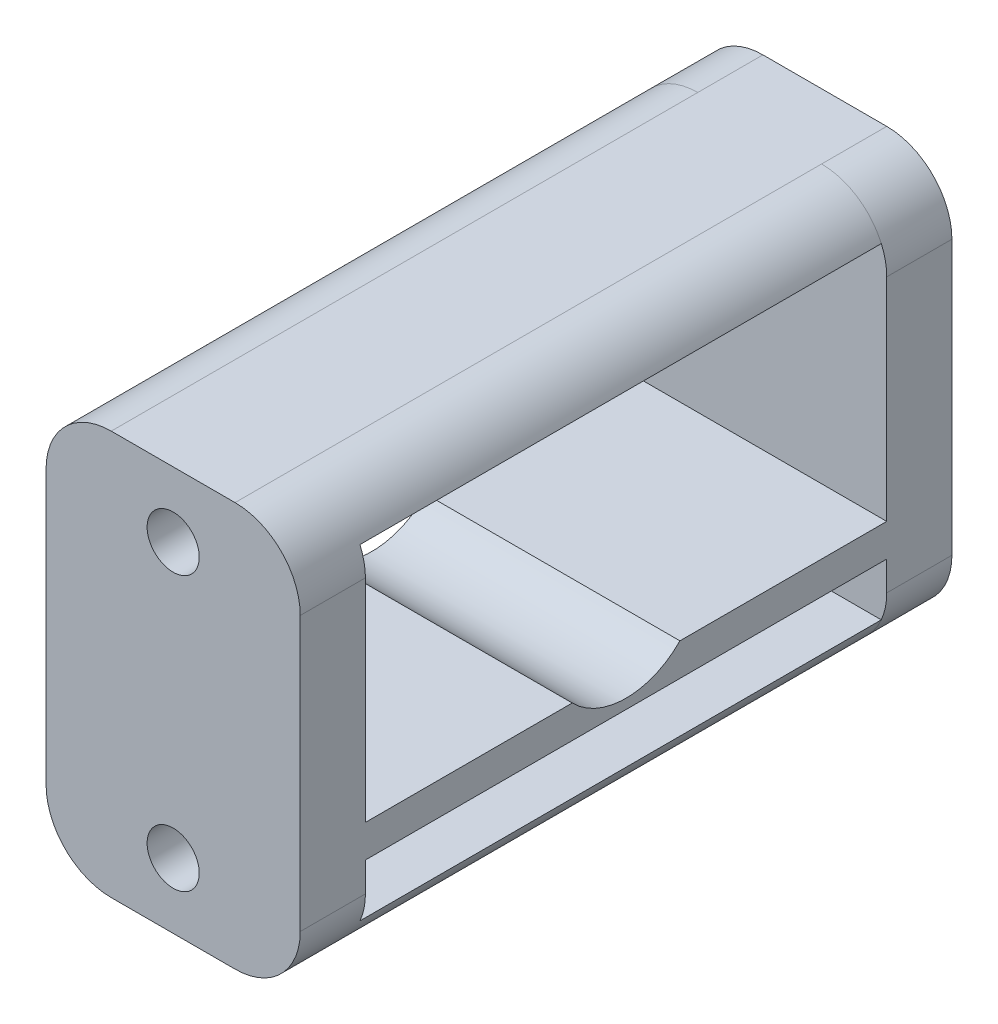
SolidWorks part; units mm, degrees
ref_plane "Plan de face" through (0, 0, 0) normal (0, 0, 1) x (1, 0, 0)
ref_plane "Plan de dessus" through (0, 0, 0) normal (0, 1, 0) x (1, 0, 0)
ref_plane "Plan de droite" through (0, 0, 0) normal (1, 0, 0) x (0, 0, -1)
sketch "Esquisse1" plane through (0, 0, 0) normal (0, 0, 1) x (1, 0, 0)
  line L1 (-19.5, -31) -> (19.5, -31)
  line L2 (-19.5, -31) -> (-19.5, 31)
  line L3 (-19.5, 31) -> (19.5, 31)
  line L4 (19.5, -31) -> (19.5, 31)
  line L5 (-19.5, -31) -> (19.5, 31) construction
  line L6 (-19.5, 31) -> (19.5, -31) construction
  point P0 (0, 0)
  dimension "D1" = 62
  dimension "D2" = 39
extrude "Boss.-Extru.1" add sketch "Esquisse1" along normal blind 10 contours L2 L1 L4 L3
sketch "Esquisse2" plane through (0, 0, 10) normal (0, 0, 1) x (1, 0, 0)
  line L0 (0, 31) -> (0, 21) construction
  line L1 (-19.5, 31) -> (19.5, 31) construction
  line L2 (0, -31) -> (0, -21) construction
  line L3 (-19.5, -31) -> (19.5, -31) construction
  circle A0 centre (0, 21) radius 4
  circle A1 centre (0, -21) radius 4
  dimension "D3" = 8
  dimension "D4" = 8
  dimension "D1" = 10
  dimension "D2" = 10
extrude "Enlèv. mat.-Extru.1" cut sketch "Esquisse2" against normal blind 10
fillet "Congé1" radius 10 4 edges at (-19.5, -31, 5) (19.5, -31, 5) (19.5, 31, 5) (-19.5, 31, 5)
sketch "Esquisse3" plane through (0, 0, 10) normal (0, 0, 1) x (1, 0, 0)
  line L0 (0, 25) -> (19.5, 25)
  line L1 (19.5, 25) -> (19.5, 31)
  line L2 (19.5, 31) -> (-19.5, 31)
  line L3 (-19.5, 31) -> (-19.5, 25)
  line L4 (-19.5, 25) -> (0, 25)
  line L5 (19.5, -21) -> (19.5, 21) construction
  line L6 (0, -25) -> (19.5, -25)
  line L7 (19.5, -25) -> (19.5, -31)
  line L8 (19.5, -31) -> (-19.5, -31)
  line L9 (-19.5, -31) -> (-19.5, -25)
  line L10 (-19.5, -25) -> (0, -25)
  line L11 (-9.5, -31) -> (9.5, -31) construction
  circle A0 centre (0, 21) radius 4 construction
  circle A1 centre (0, -21) radius 4 construction
  dimension "D1" = 39
  dimension "D2" = 0
  dimension "D3" = 0
extrude "Boss.-Extru.2" add sketch "Esquisse3" along normal blind 80
fillet "Congé2" radius 10 4 edges at (-19.5, 31, 50) (19.5, 31, 50) (-19.5, -31, 50) (19.5, -31, 50)
sketch "Esquisse4" plane through (0, 0, 90) normal (0, 0, 1) x (1, 0, 0)
  line L1 (-19.5, -31) -> (19.5, -31)
  line L2 (-19.5, -31) -> (-19.5, 31)
  line L3 (-19.5, 31) -> (19.5, 31)
  line L4 (19.5, -31) -> (19.5, 31)
  line L5 (-19.5, -31) -> (19.5, 31) construction
  line L6 (-19.5, 31) -> (19.5, -31) construction
  point P0 (0, 0)
  dimension "D1" = 62
  dimension "D2" = 39
extrude "Boss.-Extru.3" add sketch "Esquisse4" along normal blind 10
fillet "Congé3" radius 10 4 edges at (19.5, -31, 95) (-19.5, -31, 95) (19.5, 31, 95) (-19.5, 31, 95)
sketch "Esquisse5" plane through (0, 0, 90) normal (0, 0, -1) x (-1, 0, 0)
  circle A0 centre (0, 21) radius 4
  circle A1 centre (0, -21) radius 4
extrude "Enlèv. mat.-Extru.2" cut sketch "Esquisse5" against normal blind 100
sketch "Esquisse6" plane through (0, 0, 90) normal (0, 0, -1) x (-1, 0, 0)
  line L0 (-19.5, -21) -> (-19.5, 21) construction
  line L1 (-19.5, -16.5) -> (19.5, -16.5)
  line L2 (-19.5, -16.5) -> (-19.5, -11.5)
  line L3 (-19.5, -11.5) -> (19.5, -11.5)
  line L4 (19.5, -16.5) -> (19.5, -11.5)
  line L5 (19.5, -21) -> (19.5, 21) construction
  circle A0 centre (0, -21) radius 4 construction
  dimension "D1" = 4.5
  dimension "D2" = 5
extrude "Boss.-Extru.4" add sketch "Esquisse6" along normal blind 80
sketch "Esquisse7" plane through (-19.5, 0, 0) normal (-1, 0, 0) x (0, 0, 1)
  line L0 (50, -16.5) -> (50, -3.5) construction
  line L1 (10, -16.5) -> (90, -16.5) construction
  circle A0 centre (50, -3.5) radius 11.5
  point P6 (0, 0)
  dimension "D1" = 23
  dimension "D2" = 13
extrude "Enlèv. mat.-Extru.3" cut sketch "Esquisse7" against normal through all
